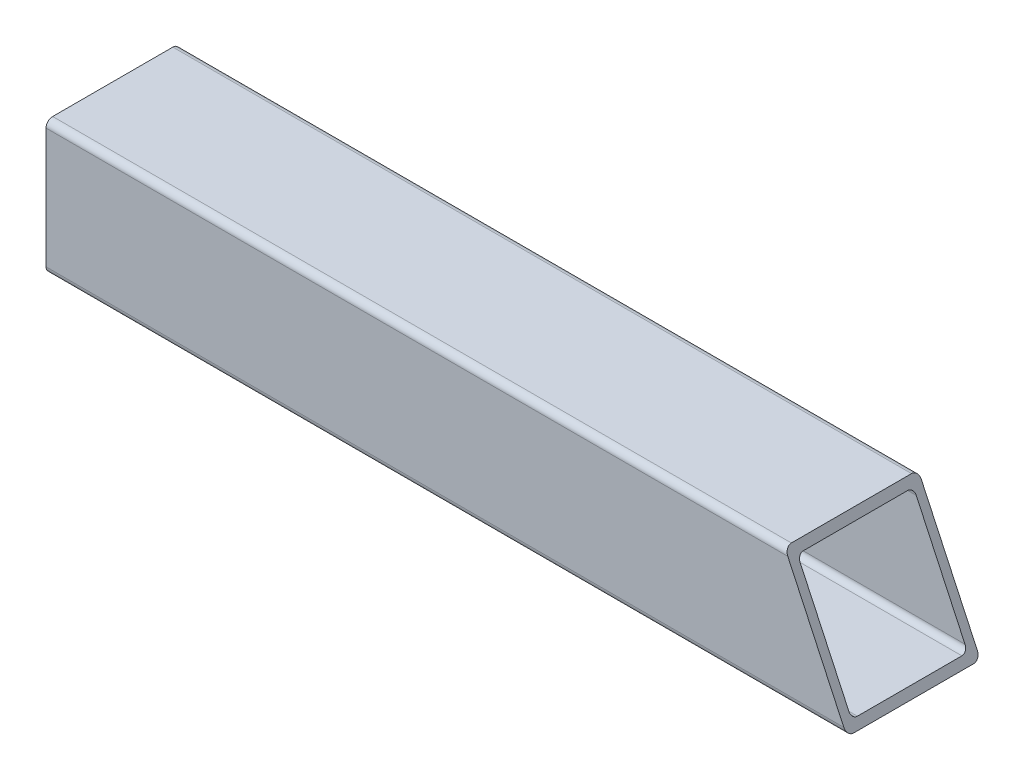
SolidWorks part; units mm, degrees
ref_plane "Front" through (0, 0, 0) normal (0, 0, 1) x (1, 0, 0)
ref_plane "Top" through (0, 0, 0) normal (0, 1, 0) x (1, 0, 0)
ref_plane "Right" through (0, 0, 0) normal (1, 0, 0) x (0, 0, -1)
sketch "Sketch1" plane through (0, 0, 0) normal (1, 0, 0) x (0, 0, -1)
  line L0 (-11.049, 0) -> (-12.7, 0) construction
  line L1 (11.43, -12.7) -> (-11.43, -12.7) construction
  line L2 (12.7, -11.43) -> (12.7, 11.43) construction
  line L3 (11.43, 12.7) -> (-11.43, 12.7) construction
  line L4 (-12.7, -11.43) -> (-12.7, 11.43) construction
  line L5 (12.7, -12.7) -> (-12.7, 12.7) construction
  line L6 (12.7, 12.7) -> (-12.7, -12.7) construction
  line L7 (9.9441, 11.049) -> (-9.9441, 11.049) construction
  line L8 (11.049, 9.9441) -> (11.049, -9.9441) construction
  line L9 (9.9441, -11.049) -> (-9.9441, -11.049) construction
  line L10 (-11.049, 9.9441) -> (-11.049, -9.9441) construction
  line L11 (11.049, 11.049) -> (-11.049, -11.049) construction
  line L12 (11.049, -11.049) -> (-11.049, 11.049) construction
  line L13 (0, -11.049) -> (0, -12.7) construction
  line L14 (11.049, -9.9441) -> (11.049, -12.7) construction
  line L15 (11.049, 0) -> (12.7, 0) construction
  line L16 (11.049, -12.7) -> (12.7, -12.7) construction
  arc A0 (-9.9441, -11.049) -> (-11.049, -9.9441) centre (-9.9441, -9.9441) cw construction
  arc A1 (11.049, -9.9441) -> (9.9441, -11.049) centre (9.9441, -9.9441) cw construction
  arc A2 (9.9441, 11.049) -> (11.049, 9.9441) centre (9.9441, 9.9441) cw construction
  arc A3 (-9.9441, 11.049) -> (-11.049, 9.9441) centre (-9.9441, 9.9441) ccw construction
  arc A4 (11.43, -12.7) -> (12.7, -11.43) centre (11.43, -11.43) ccw construction
  arc A5 (12.7, 11.43) -> (11.43, 12.7) centre (11.43, 11.43) ccw construction
  arc A6 (-11.43, 12.7) -> (-12.7, 11.43) centre (-11.43, 11.43) ccw construction
  arc A7 (-11.43, -12.7) -> (-12.7, -11.43) centre (-11.43, -11.43) cw construction
  point P0 (0, 0)
  point P6 (0, 0)
  dimension "D2" = 1.1049
  dimension "D3" = 1.27
  dimension "Outside Width" = 25.4
  dimension "Ouside Height" = 25.4
  dimension "Inside Height" = 22.098
  dimension "Wall Thickness" = 1.651
sketch "Sketch2" plane through (0, 0, 0) normal (0, 0, 1) x (1, 0, 0)
  line L0 (-76.2, 0) -> (76.2, 0) construction
  point P3 (-52.451, 0)
  point P4 (52.451, 0)
  dimension "Length" = 152.4
  dimension "D1" = 23.749
  dimension "D2" = 23.749
sketch "Sketch4" plane through (0, 0, 0) normal (1, 0, 0) x (0, 0, -1)
  line L8 (12.7, -11.43) -> (12.7, 11.43)
  line L9 (11.43, 12.7) -> (-11.43, 12.7)
  line L10 (-12.7, -11.43) -> (-12.7, 11.43)
  line L11 (11.43, -12.7) -> (-11.43, -12.7)
  line L12 (11.049, 9.9441) -> (11.049, -9.9441)
  line L13 (9.9441, -11.049) -> (-9.9441, -11.049)
  line L14 (-11.049, 9.9441) -> (-11.049, -9.9441)
  line L15 (9.9441, 11.049) -> (-9.9441, 11.049)
  arc A8 (12.7, 11.43) -> (11.43, 12.7) centre (11.43, 11.43) ccw
  arc A9 (-11.43, 12.7) -> (-12.7, 11.43) centre (-11.43, 11.43) ccw
  arc A10 (-12.7, -11.43) -> (-11.43, -12.7) centre (-11.43, -11.43) ccw
  arc A11 (11.43, -12.7) -> (12.7, -11.43) centre (11.43, -11.43) ccw
  arc A12 (9.9441, -11.049) -> (11.049, -9.9441) centre (9.9441, -9.9441) ccw
  arc A13 (-11.049, -9.9441) -> (-9.9441, -11.049) centre (-9.9441, -9.9441) ccw
  arc A14 (-9.9441, 11.049) -> (-11.049, 9.9441) centre (-9.9441, 9.9441) ccw
  arc A15 (11.049, 9.9441) -> (9.9441, 11.049) centre (9.9441, 9.9441) ccw
extrude "Boss-Extrude1" add sketch "Sketch4" along normal up to vertex (-76.2 mm away) and the other way up to vertex (-76.2 mm away) up to point (-76.2, 0, 0) other way up to point (76.2, 0, 0)
sketch "Sketch5" plane through (0, 0, 12.7) normal (0, 0, 1) x (1, 0, 0)
  line L0 (76.2, -12.7) -> (64.3558, 12.7)
  line L1 (76.2, 12.7) -> (-76.2, 12.7) construction
  line L2 (64.3558, 12.7) -> (76.2, 12.7)
  line L3 (76.2, 12.7) -> (76.2, -12.7)
  dimension "D1" = 25
extrude "Cut-Extrude1" cut sketch "Sketch5" against normal through all
equation "\"D3@Sketch1\"=\"Outside Width@Sketch1\"*.05"
equation "\"D2@Sketch1\" = \"Inside Height@Sketch1\" * .05"
equation "\"D1@Sketch2\"=\"Outside Width@Sketch1\"-\"Wall Thickness@Sketch1\""
equation "\"D2@Sketch2\"=\"D1@Sketch2\""
